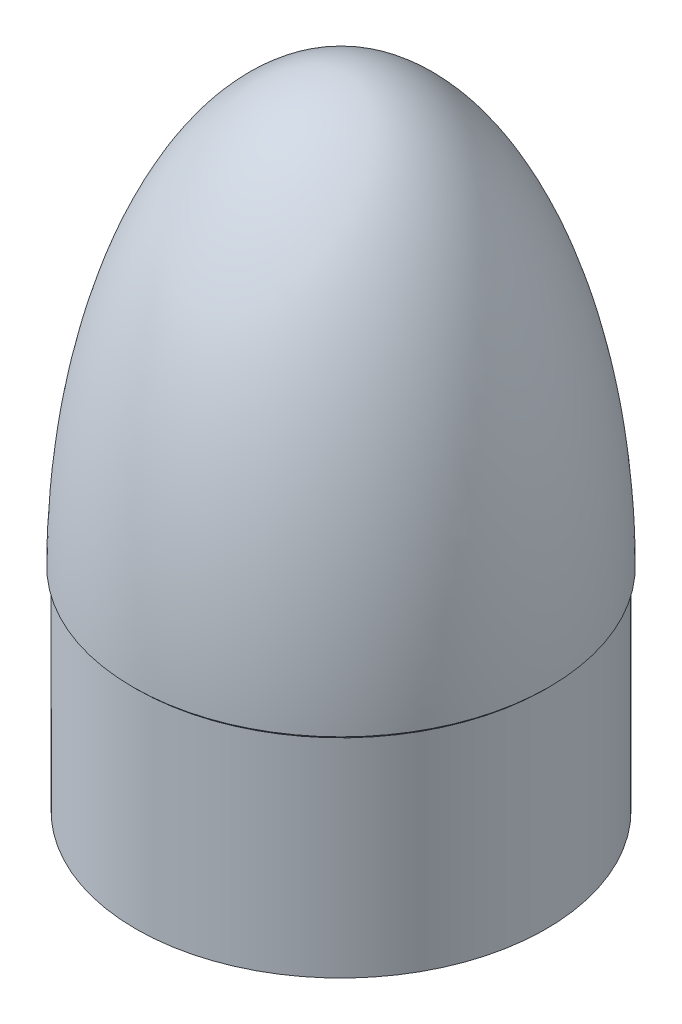
SolidWorks part; units mm, degrees
ref_plane "Front Plane" through (0, 0, 0) normal (0, 0, 1) x (1, 0, 0)
ref_plane "Top Plane" through (0, 0, 0) normal (0, 1, 0) x (1, 0, 0)
ref_plane "Right Plane" through (0, 0, 0) normal (1, 0, 0) x (0, 0, -1)
sketch "Sketch1" plane through (0, 0, 0) normal (0, 0, 1) x (1, 0, 0)
  line L3 (0, 0) -> (0, 202.3003) construction
  line L5 (0, 165.1) -> (0, 162.1028)
  line L10 (76.3778, 0) -> (76.3778, -81.661)
  line L12 (76.3778, -81.661) -> (79.375, -81.661)
  line L13 (79.375, -81.661) -> (79.375, -1.143)
  line L14 (80.518, 0) -> (79.375, -1.143)
  line L15 (79.375, -1.143) -> (80.518, -1.143) construction
  ellipse E0 centre (0, 0) end of major axis (0, 162.1028) minor radius 76.3778 (76.3778, 0) -> (0, 162.1028) ccw
  ellipse E1 centre (0, 0) end of major axis (0, -165.1) minor radius 80.518 (80.518, 0) -> (0, 165.1) ccw
  point P19 (0, 0)
  dimension "D1" = 158.75
  dimension "D2" = 80.518
  dimension "D3" = 165.1
  dimension "D4" = 161.036
  dimension "D5" = 2.9972
  dimension "D6" = 2.9972
  dimension "D7" = 45
revolve "Revolve1" add sketch "Sketch1" angle 360 about L5
